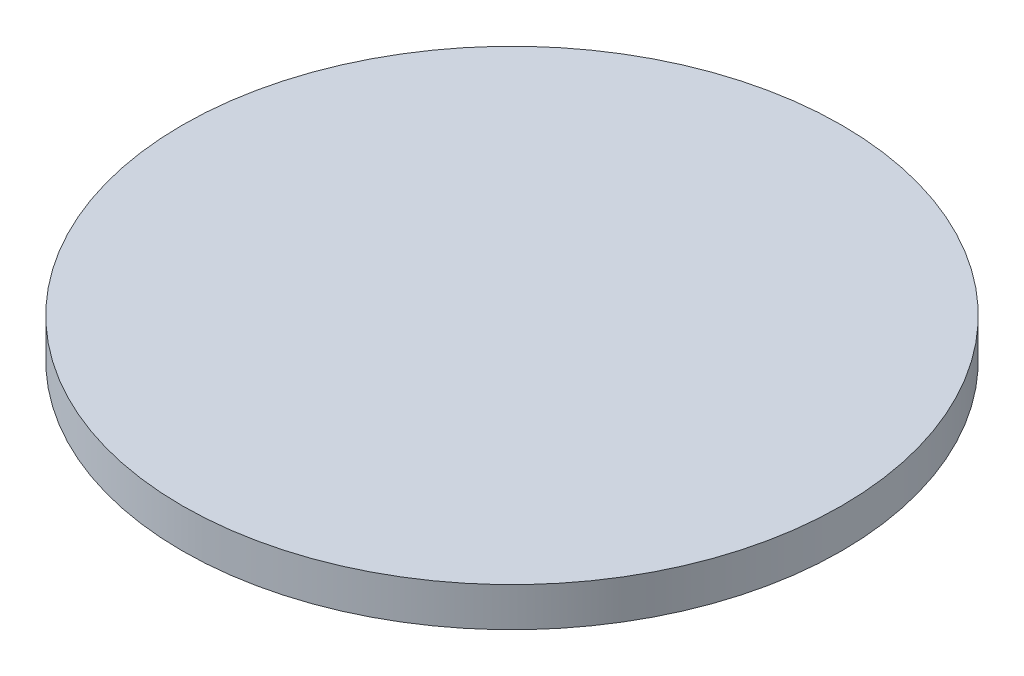
SolidWorks part; units mm, degrees
material "1060 Alloy"
ref_plane "Front Plane" through (0, 0, 0) normal (0, 0, 1) x (1, 0, 0)
ref_plane "Top Plane" through (0, 0, 0) normal (0, 1, 0) x (1, 0, 0)
ref_plane "Right Plane" through (0, 0, 0) normal (1, 0, 0) x (0, 0, -1)
sketch "Sketch1" plane through (0, 0, 0) normal (0, 1, 0) x (1, 0, 0)
  circle A0 centre (0, 0) radius 16.875
  dimension "D1" = 33.75
extrude "Boss-Extrude1" add sketch "Sketch1" along normal blind 1
sketch "Sketch2" plane through (0, 0, 0) normal (0, -1, 0) x (1, 0, 0)
  circle A0 centre (0, 0) radius 16.875
  circle A1 centre (0, 0) radius 15.875
  circle A2 centre (0, 0) radius 16.875 construction
  dimension "D1" = 0
  dimension "D2" = 31.75
extrude "Boss-Extrude2" add sketch "Sketch2" along normal blind 1
thread "Thread1" pitch 0.25 method cut profile "Thread Profile1" start angle 0, offset 0, length 1, pitch 0.25, diameter 31.75
ref_plane "Plane1" through (15.875, -1, 0) normal (0, 0, 1) x (1, 0, 0)
sketch "Thread Profile1" plane through (15.875, -1, 0) normal (0, 0, 1) x (1, 0, 0)
  line L0 (0, 0) -> (0, 0.25) construction
  line L1 (0, 0) -> (0.1353, 0.0781)
  line L2 (0.1353, 0.0781) -> (0.1353, 0.1094)
  line L3 (0.1353, 0.1094) -> (0, 0.1875)
  line L4 (0.1353, 0.0937) -> (0, 0.0937) construction
  line L11 (0, 0) -> (0, 0.1875)
  point P2 (0, 0)
  dimension "Pitch" = 0.25
  dimension "Profile_Angle" = 60
  dimension "Profile_Land" = 0.0312
  dimension "Profile_Height" = 0.1353
sketch "Sketch3" plane through (0, 0, 0) normal (0, -1, 0) x (1, 0, 0)
  circle A0 centre (0, 0) radius 14.44
  dimension "D1" = 28.88
extrude "Boss-Extrude3" add sketch "Sketch3" along normal blind 1
